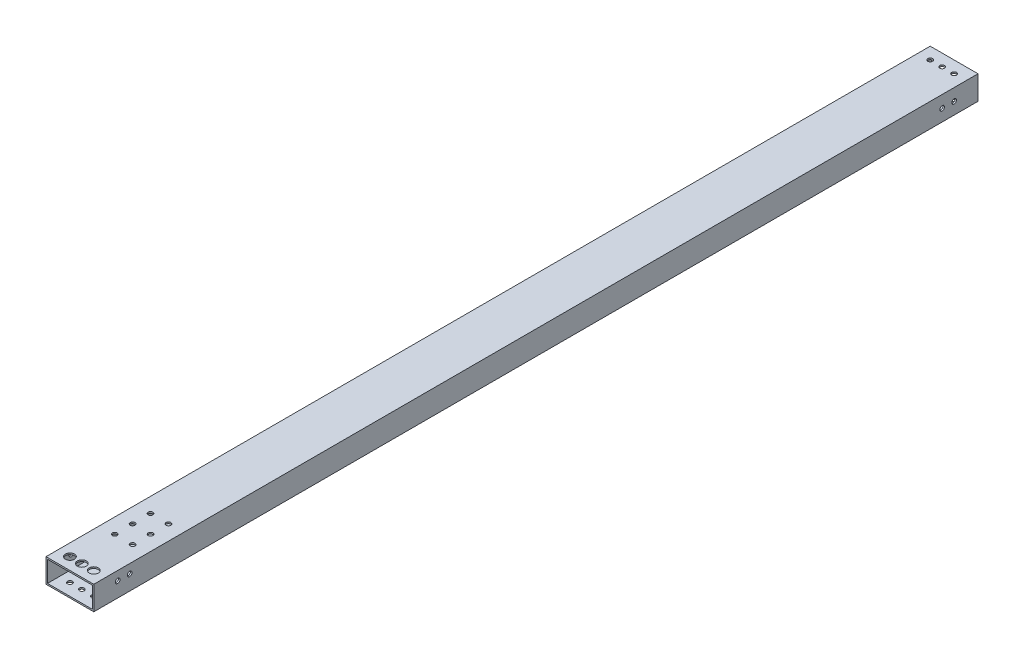
SolidWorks part; units mm, degrees
material "6061-T6 (SS)"
ref_plane "Front Plane" through (0, 0, 0) normal (0, 0, 1) x (1, 0, 0)
ref_plane "Top Plane" through (0, 0, 0) normal (0, 1, 0) x (1, 0, 0)
ref_plane "Right Plane" through (0, 0, 0) normal (1, 0, 0) x (0, 0, -1)
sketch "Sketch1" plane through (0, 0, 0) normal (0, 0, 1) x (1, 0, 0)
  line L0 (-23.8125, 11.1125) -> (23.8125, 11.1125)
  line L1 (-25.4, -12.7) -> (25.4, -12.7)
  line L2 (-25.4, -12.7) -> (-25.4, 12.7)
  line L3 (-25.4, 12.7) -> (25.4, 12.7)
  line L4 (25.4, -12.7) -> (25.4, 12.7)
  line L5 (-25.4, -12.7) -> (25.4, 12.7) construction
  line L6 (-25.4, 12.7) -> (25.4, -12.7) construction
  line L7 (23.8125, -11.1125) -> (23.8125, 11.1125)
  line L8 (-23.8125, -11.1125) -> (23.8125, -11.1125)
  line L9 (-23.8125, -11.1125) -> (-23.8125, 11.1125)
  point P0 (0, 0)
  dimension "D1" = 50.8
  dimension "D2" = 25.4
  dimension "D3" = 1.5875
extrude "Boss-Extrude1" add sketch "Sketch1" along normal mid plane 939.8
sketch "Sketch4" plane through (0, 12.7, 0) normal (0, 1, 0) x (1, 0, 0)
  line L0 (25.4, -469.9) -> (-25.4, -469.9) construction
  circle A0 centre (-12.7, -457.2) radius 4.826
  circle A1 centre (0, -457.2) radius 4.826
  circle A2 centre (12.7, -457.2) radius 4.826
  dimension "D1" = 9.652
  dimension "D2" = 12.7
  dimension "D3" = 12.7
  dimension "D4" = 12.7
extrude "Cut-Extrude3" cut sketch "Sketch4" against normal up to surface (1.5875 mm away) contours A0 | A1 | A2 region at (-12.7, 12.7, 457.2) region at (0, 12.7, 457.2) region at (12.7, 12.7, 457.2) up to face at (0, 11.1125, 0)
sketch "Sketch5" plane through (0, -12.7, 0) normal (0, -1, 0) x (1, 0, 0)
  circle A0 centre (-12.7, 457.2) radius 4.826 construction
  circle A1 centre (0, 457.2) radius 4.826 construction
  circle A2 centre (12.7, 457.2) radius 4.826 construction
  circle A3 centre (-12.7, 457.2) radius 4.826
  circle A4 centre (0, 457.2) radius 4.826
  circle A5 centre (12.7, 457.2) radius 4.826
  circle A6 centre (-12.7, 457.2) radius 2.5527
  circle A7 centre (0, 457.2) radius 2.5527
  circle A8 centre (12.7, 457.2) radius 2.5527
  dimension "D1" = 5.1054
extrude "Cut-Extrude4" cut sketch "Sketch5" against normal up to surface (1.5875 mm away) contours A8 | A7 | A6 region at (-12.7, -12.7, 457.2) region at (0, -12.7, 457.2) region at (12.7, -12.7, 457.2) up to face at (0, -11.1125, 0)
sketch "Sketch6" plane through (0, -12.7, 0) normal (0, -1, 0) x (1, 0, 0)
  line L0 (-25.4, -469.9) -> (25.4, -469.9) construction
  circle A0 centre (-12.7, -457.2) radius 2.5527
  circle A1 centre (0, -457.2) radius 2.5527
  circle A2 centre (12.7, -457.2) radius 2.5527
  dimension "D1" = 5.1054
  dimension "D2" = 12.7
  dimension "D3" = 12.7
  dimension "D4" = 12.7
extrude "Cut-Extrude5" cut sketch "Sketch6" against normal through all contours A2 | A1 | A0 region at (-12.7, -12.7, -457.2) region at (0, -12.7, -457.2) region at (12.7, -12.7, -457.2)
sketch "Sketch7" plane through (25.4, 0, 0) normal (1, 0, 0) x (0, 0, -1)
  line L0 (-469.9, -12.7) -> (-469.9, 12.7) construction
  line L2 (469.9, -12.7) -> (469.9, 12.7) construction
  line L3 (-469.9, -12.7) -> (469.9, -12.7) construction
  circle A0 centre (-457.2, 3.175) radius 2.4892
  circle A1 centre (-444.5, 3.175) radius 2.4892
  circle A2 centre (-431.8, 3.175) radius 2.4892
  circle A3 centre (-419.1, 3.175) radius 2.4892
  circle A4 centre (457.2, 0) radius 2.4892
  circle A5 centre (444.5, 0) radius 2.4892
  circle A6 centre (431.8, 0) radius 2.4892
  dimension "D1" = 4.9784
  dimension "D7" = 4.9784
  dimension "D8" = 12.7
  dimension "D2" = 12.7
  dimension "D3" = 12.7
  dimension "D4" = 12.7
  dimension "D5" = 12.7
  dimension "D6" = 15.875
  dimension "D9" = 12.7
  dimension "D10" = 12.7
  dimension "D11" = 12.7
extrude "Cut-Extrude6" cut sketch "Sketch7" against normal through all contours A6 | A5 | A1 | A2 region at (25.4, 3.175, 444.5) region at (25.4, 3.175, 431.8) region at (25.4, 0, -444.5) region at (25.4, 0, -431.8)
sketch "Sketch9" plane through (0, 12.7, 0) normal (0, 1, 0) x (1, 0, 0)
  line L0 (25.4, -469.9) -> (-25.4, -469.9) construction
  circle A0 centre (-12.7, -419.1) radius 2.5527
  circle A1 centre (0, -419.1) radius 2.5527
  circle A2 centre (12.7, -419.1) radius 2.5527
  dimension "D1" = 5.1054
  dimension "D2" = 12.7
  dimension "D3" = 12.7
  dimension "D4" = 50.8
extrude "Cut-Extrude7" [suppressed] cut sketch "Sketch9" against normal through all
sketch "Sketch10" plane through (0, 12.7, 0) normal (0, 1, 0) x (1, 0, 0)
  line L0 (0, -469.9) -> (0, 469.9) construction
  line L1 (25.4, -469.9) -> (-25.4, -469.9) construction
  line L2 (25.4, 469.9) -> (-25.4, 469.9) construction
  circle A0 centre (-9.525, -412.75) radius 2.5527
  circle A1 centre (-9.525, -393.7) radius 2.5527
  circle A2 centre (-9.525, -374.65) radius 2.5527
  circle A3 centre (9.525, -374.65) radius 2.5527
  circle A4 centre (9.525, -393.7) radius 2.5527
  circle A5 centre (9.525, -412.75) radius 2.5527
  dimension "D1" = 5.1054
  dimension "D2" = 9.525
  dimension "D3" = 9.525
  dimension "D4" = 57.15
  dimension "D5" = 19.05
  dimension "D6" = 19.05
extrude "Cut-Extrude8" cut sketch "Sketch10" against normal through all
